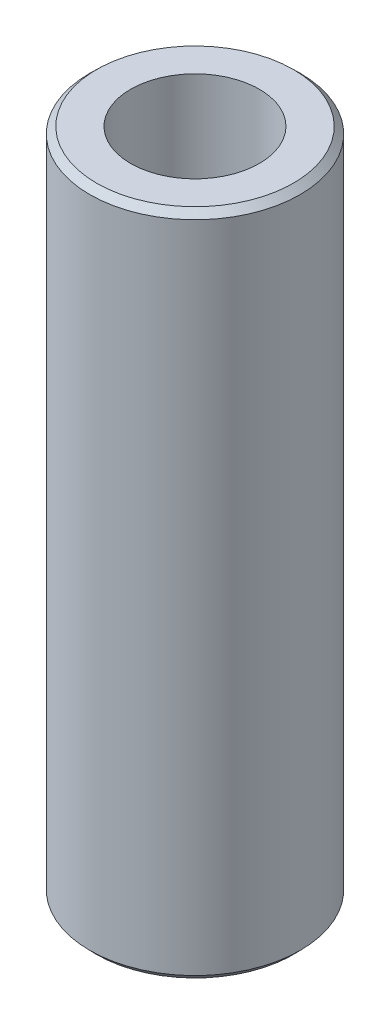
SolidWorks part; units mm, degrees
ref_plane "Front Plane" through (0, 0, 0) normal (0, 0, 1) x (1, 0, 0)
ref_plane "Top Plane" through (0, 0, 0) normal (0, 1, 0) x (1, 0, 0)
ref_plane "Right Plane" through (0, 0, 0) normal (1, 0, 0) x (0, 0, -1)
sketch "Sketch1" plane through (0, 0, 0) normal (0, 1, 0) x (1, 0, 0)
  circle A0 centre (0, 0) radius 7.5
  dimension "SHAFT_OD" = 15
extrude "Boss-Extrude1" add sketch "Sketch1" along normal blind 47.6238
sketch "Sketch2" plane through (0, 0, 0) normal (0, 1, 0) x (1, 0, 0)
  circle A0 centre (0, 0) radius 4.5896
  dimension "BORE_D" = 9.1793
extrude "Cut-Extrude1" cut sketch "Sketch2" along normal through all
chamfer "Chamfer1" distance 0.4661 angle 45.832 2 edges at (0, 47.6238, 7.5) (0, 0, 7.5) first distance on face at (0, 47.6238, 7.5) first distance on face at (0, 0, 4.5896)
